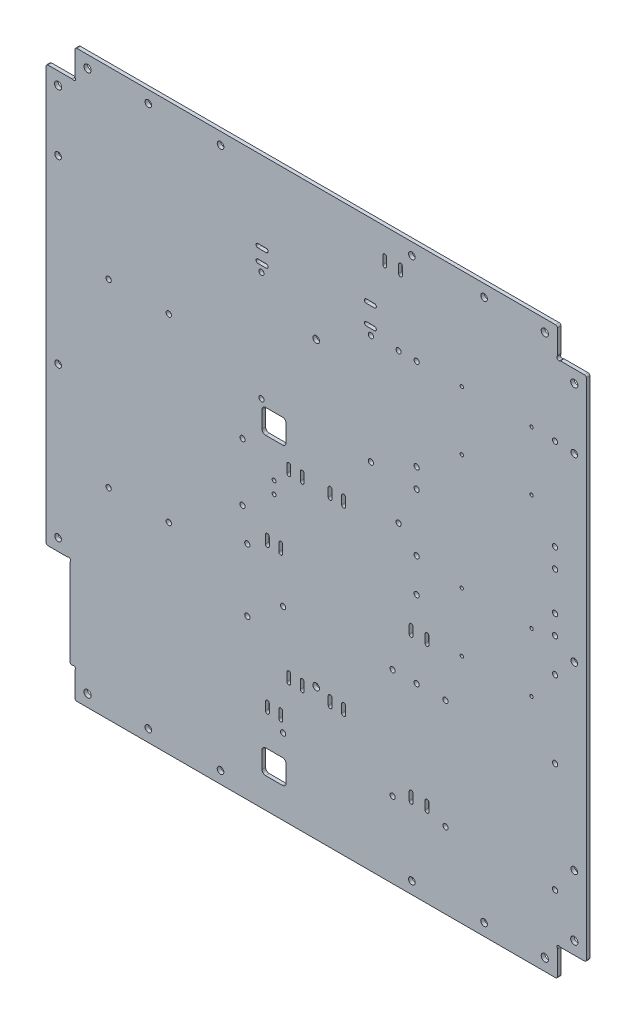
SolidWorks part; units mm, degrees
material "Acrylic (Medium-high impact)"
ref_plane "Front" through (0, 0, 0) normal (0, 0, 1) x (1, 0, 0)
ref_plane "Top" through (0, 0, 0) normal (0, 1, 0) x (1, 0, 0)
ref_plane "Right" through (0, 0, 0) normal (1, 0, 0) x (0, 0, -1)
sketch "Sketch2" plane through (0, 0, 0) normal (0, 0, 1) x (1, 0, 0)
  line L1 (0, 0) -> (449, 0)
  line L2 (0, 0) -> (0, 470)
  line L3 (0, 470) -> (449, 470)
  line L4 (449, 0) -> (449, 470)
  dimension "D1" = 449
  dimension "D2" = 470
extrude "Boss-Extrude1" add sketch "Sketch2" along normal blind 3
sketch "Sketch23" plane through (0, 0, 0) normal (0, 0, -1) x (-1, 0, 0)
  line L0 (-449, 470) -> (0, 470) construction
  line L1 (-449, 470) -> (-429, 470)
  line L2 (-449, 470) -> (-449, 450)
  line L3 (-449, 450) -> (-429, 450)
  line L4 (-429, 470) -> (-429, 450)
  line L5 (0, 470) -> (-20, 470)
  line L6 (0, 470) -> (0, 450)
  line L7 (0, 450) -> (-20, 450)
  line L8 (-20, 470) -> (-20, 450)
  line L9 (0, 470) -> (0, 0) construction
  line L11 (0, 0) -> (-20, 0)
  line L12 (0, 0) -> (0, 20)
  line L13 (0, 20) -> (-20, 20)
  line L14 (-20, 0) -> (-20, 20)
  line L15 (-449, 0) -> (-429, 0)
  line L16 (-449, 0) -> (-449, 20)
  line L17 (-449, 20) -> (-429, 20)
  line L18 (-429, 0) -> (-429, 20)
  dimension "D1" = 20
  dimension "D2" = 20
hole_wizard "M5 Clearance Hole1" positions "Sketch4" profile "Sketch5" hole size "M5" standard "ANSI Metric" end condition up to next
sketch "Sketch4" plane through (0, 0, 0) normal (0, 0, -1) x (-1, 0, 0)
  line L0 (-224.5, 470) -> (-224.5, 0) construction
  line L1 (-449, 470) -> (0, 470) construction
  line L2 (0, 0) -> (-449, 0) construction
  line L3 (-429, 460) -> (-364, 460) construction
  line L6 (-364, 460) -> (-85, 460) construction
  line L7 (-85, 460) -> (-20, 460) construction
  line L9 (-449, 235) -> (0, 235) construction
  line L10 (-449, 0) -> (-449, 470) construction
  line L12 (0, 470) -> (0, 0) construction
  line L13 (-439, 450) -> (-439, 20) construction
  line L18 (-10, 450) -> (-10, 20) construction
  line L21 (-429, 10) -> (-20, 10) construction
  line L31 (-20, 470) -> (-20, 450) construction
  line L32 (-429, 470) -> (-429, 450) construction
  line L33 (-449, 450) -> (-429, 450) construction
  line L34 (-449, 20) -> (-429, 20) construction
  line L35 (-429, 0) -> (-429, 20) construction
  line L36 (0, 450) -> (-20, 450) construction
  line L37 (0, 20) -> (-20, 20) construction
  line L38 (-20, 0) -> (-20, 20) construction
  point P13 (-224.5, 360)
  point P17 (-224.5, 110)
  point P24 (-364, 460)
  point P29 (-85, 460)
  point P54 (-304, 460)
  point P56 (-145, 460)
  point P59 (-85, 10)
  point P60 (-145, 10)
  point P61 (-304, 10)
  point P62 (-364, 10)
  point P83 (-439, 385)
  point P85 (-439, 85)
  point P92 (-10, 110)
  point P93 (-10, 385)
  point P97 (-439, 235)
  point P103 (-10, 235)
  dimension "D5" = 65
  dimension "D8" = 65
  dimension "D3" = 100
  dimension "D2" = 100
  dimension "D1" = 60
  dimension "D4" = 60
  dimension "D6" = 90
  dimension "D9" = 65
sketch "Sketch5" plane through (10, 235, 0) normal (1, 0, 0) x (0, 1, 0)
  line L0 (0, 0) -> (0, 3)
  line L1 (0, 3) -> (2.75, 3)
  line L2 (2.75, 3) -> (2.75, 0)
  line L5 (2.75, 0) -> (0, 0)
  line L11 (0, -6.35) -> (0, 107.95) construction
  dimension "Thru Hole Dia." = 5.5
  dimension "Thru Hole Depth" = 3
sketch "Sketch10" plane through (0, 0, 0) normal (0, 0, -1) x (-1, 0, 0)
  line L0 (-20, 20) -> (-429, 20) construction
  line L1 (-114.5, 26) -> (-69.5, 26) construction
  line L2 (-114.5, 26) -> (-114.5, 52) construction
  line L3 (-114.5, 52) -> (-69.5, 52) construction
  line L4 (-69.5, 26) -> (-69.5, 52) construction
  line L5 (-169.5, 45.65) -> (-175.85, 45.65)
  line L6 (-169.5, 52) -> (-214.5, 52) construction
  line L7 (-224.5, 20) -> (-224.5, 145.1565) construction
  line L8 (-108.15, 52) -> (-108.15, 45.65)
  line L13 (-169.5, 52) -> (-169.5, 26) construction
  line L15 (-119.5, 52) -> (-164.5, 52) construction
  line L16 (-119.5, 52) -> (-119.5, 26) construction
  line L17 (-119.5, 26) -> (-164.5, 26) construction
  line L18 (-164.5, 52) -> (-164.5, 26) construction
  line L22 (-108.15, 45.65) -> (-114.5, 45.65)
  line L23 (-114.5, 45.65) -> (-114.5, 32.35)
  line L24 (-114.5, 32.35) -> (-108.15, 32.35)
  line L25 (-108.15, 32.35) -> (-108.15, 26)
  line L26 (-108.15, 26) -> (-75.85, 26)
  line L27 (-75.85, 26) -> (-75.85, 32.35)
  line L28 (-75.85, 32.35) -> (-69.5, 32.35)
  line L29 (-69.5, 32.35) -> (-69.5, 45.65)
  line L30 (-69.5, 45.65) -> (-75.85, 45.65)
  line L31 (-75.85, 45.65) -> (-75.85, 52)
  line L32 (-75.85, 52) -> (-108.15, 52)
  line L33 (-158.15, 52) -> (-158.15, 45.65)
  line L34 (-158.15, 45.65) -> (-164.5, 45.65)
  line L35 (-164.5, 45.65) -> (-164.5, 32.35)
  line L36 (-164.5, 32.35) -> (-158.15, 32.35)
  line L37 (-158.15, 32.35) -> (-158.15, 26)
  line L38 (-158.15, 26) -> (-125.85, 26)
  line L39 (-125.85, 26) -> (-125.85, 32.35)
  line L40 (-125.85, 32.35) -> (-119.5, 32.35)
  line L41 (-119.5, 32.35) -> (-119.5, 45.65)
  line L42 (-119.5, 45.65) -> (-125.85, 45.65)
  line L43 (-125.85, 45.65) -> (-125.85, 52)
  line L44 (-125.85, 52) -> (-158.15, 52)
  line L45 (-284.5, 52) -> (-284.5, 26) construction
  line L46 (-329.5, 26) -> (-284.5, 26) construction
  line L47 (-329.5, 52) -> (-329.5, 26) construction
  line L48 (-329.5, 52) -> (-284.5, 52) construction
  line L49 (-379.5, 26) -> (-379.5, 52) construction
  line L50 (-334.5, 52) -> (-379.5, 52) construction
  line L51 (-334.5, 26) -> (-334.5, 52) construction
  line L52 (-334.5, 26) -> (-379.5, 26) construction
  line L53 (-323.15, 52) -> (-290.85, 52)
  line L54 (-323.15, 45.65) -> (-323.15, 52)
  line L55 (-329.5, 45.65) -> (-323.15, 45.65)
  line L56 (-329.5, 32.35) -> (-329.5, 45.65)
  line L57 (-323.15, 32.35) -> (-329.5, 32.35)
  line L58 (-323.15, 26) -> (-323.15, 32.35)
  line L59 (-290.85, 26) -> (-323.15, 26)
  line L60 (-290.85, 32.35) -> (-290.85, 26)
  line L61 (-284.5, 32.35) -> (-290.85, 32.35)
  line L62 (-284.5, 45.65) -> (-284.5, 32.35)
  line L63 (-290.85, 45.65) -> (-284.5, 45.65)
  line L64 (-290.85, 52) -> (-290.85, 45.65)
  line L65 (-373.15, 52) -> (-340.85, 52)
  line L66 (-373.15, 45.65) -> (-373.15, 52)
  line L67 (-379.5, 45.65) -> (-373.15, 45.65)
  line L68 (-379.5, 32.35) -> (-379.5, 45.65)
  line L69 (-373.15, 32.35) -> (-379.5, 32.35)
  line L70 (-373.15, 26) -> (-373.15, 32.35)
  line L71 (-340.85, 26) -> (-373.15, 26)
  line L72 (-340.85, 32.35) -> (-340.85, 26)
  line L73 (-334.5, 32.35) -> (-340.85, 32.35)
  line L74 (-334.5, 45.65) -> (-334.5, 32.35)
  line L75 (-340.85, 45.65) -> (-334.5, 45.65)
  line L76 (-340.85, 52) -> (-340.85, 45.65)
  line L77 (0, 0) -> (-449, 0) construction
  line L78 (-169.5, 26) -> (-214.5, 26) construction
  line L79 (-214.5, 52) -> (-214.5, 26) construction
  line L80 (-175.85, 45.65) -> (-175.85, 52)
  line L81 (-175.85, 52) -> (-208.15, 52)
  line L82 (-208.15, 52) -> (-208.15, 45.65)
  line L83 (-208.15, 45.65) -> (-214.5, 45.65)
  line L84 (-214.5, 45.65) -> (-214.5, 32.35)
  line L85 (-214.5, 32.35) -> (-208.15, 32.35)
  line L86 (-208.15, 32.35) -> (-208.15, 26)
  line L87 (-208.15, 26) -> (-175.85, 26)
  line L88 (-175.85, 26) -> (-175.85, 32.35)
  line L89 (-175.85, 32.35) -> (-169.5, 32.35)
  line L90 (-169.5, 32.35) -> (-169.5, 45.65)
  line L91 (-273.15, 32.35) -> (-279.5, 32.35)
  line L92 (-273.15, 26) -> (-273.15, 32.35)
  line L93 (-240.85, 26) -> (-273.15, 26)
  line L94 (-240.85, 32.35) -> (-240.85, 26)
  line L95 (-234.5, 32.35) -> (-240.85, 32.35)
  line L96 (-234.5, 45.65) -> (-234.5, 32.35)
  line L97 (-240.85, 45.65) -> (-234.5, 45.65)
  line L98 (-240.85, 52) -> (-240.85, 45.65)
  line L99 (-273.15, 52) -> (-240.85, 52)
  line L100 (-273.15, 45.65) -> (-273.15, 52)
  line L101 (-279.5, 45.65) -> (-273.15, 45.65)
  line L102 (-279.5, 32.35) -> (-279.5, 45.65)
  dimension "D2" = 45
  dimension "D4" = 26
  dimension "D1" = 6.35
  dimension "D5" = 5
  dimension "D6" = 26
  dimension "D3" = 5
  dimension "D7" = 20
extrude "extruder panel cutouts" [suppressed] cut sketch "Sketch10" against normal through all
sketch "Sketch16" [suppressed] plane through (0, 0, 0) normal (0, 0, -1) x (-1, 0, 0)
  line L0 (-373.15, 26) -> (-340.85, 26) construction
  line L1 (-366.5, 26) -> (-404.5, 26) construction
  line L2 (-366.5, 26) -> (-366.5, 52) construction
  line L3 (-366.5, 52) -> (-404.5, 52) construction
  line L4 (-404.5, 26) -> (-404.5, 52) construction
  line L6 (-398.15, 52) -> (-398.15, 45.65)
  line L7 (-398.15, 45.65) -> (-404.5, 45.65)
  line L8 (-404.5, 45.65) -> (-404.5, 32.35)
  line L9 (-404.5, 32.35) -> (-398.15, 32.35)
  line L10 (-398.15, 32.35) -> (-398.15, 26)
  line L11 (-398.15, 26) -> (-372.85, 26)
  line L12 (-372.85, 26) -> (-372.85, 32.35)
  line L13 (-372.85, 32.35) -> (-366.5, 32.35)
  line L14 (-366.5, 32.35) -> (-366.5, 45.65)
  line L15 (-366.5, 45.65) -> (-372.85, 45.65)
  line L16 (-372.85, 45.65) -> (-372.85, 52)
  line L17 (-372.85, 52) -> (-398.15, 52)
  line L18 (-449, 0) -> (-449, 470) construction
  dimension "D1" = 26
  dimension "D2" = 38
  dimension "D3" = 44.5
  dimension "D4" = 6.35
extrude "z_motor_panel_cutout" [suppressed] cut sketch "Sketch16" against normal blind 10
fillet "Fillet1" [suppressed] radius 3.175
fillet "Fillet3" [suppressed] radius 2
sketch "Sketch17" [suppressed] plane through (0, 0, 0) normal (0, 0, -1) x (-1, 0, 0)
  circle A4 centre (-376.325, 48.825) radius 1.55
  circle A5 centre (-337.675, 48.825) radius 1.55
  circle A6 centre (-337.675, 29.175) radius 1.55
  circle A7 centre (-376.325, 29.175) radius 1.55
  circle A8 centre (-326.325, 48.825) radius 1.55
  circle A9 centre (-287.675, 48.825) radius 1.55
  circle A10 centre (-287.675, 29.175) radius 1.55
  circle A11 centre (-326.325, 29.175) radius 1.55
  circle A12 centre (-161.325, 48.825) radius 1.55
  circle A13 centre (-122.675, 48.825) radius 1.55
  circle A14 centre (-122.675, 29.175) radius 1.55
  circle A15 centre (-161.325, 29.175) radius 1.55
  circle A16 centre (-111.325, 48.825) radius 1.55
  circle A17 centre (-72.675, 48.825) radius 1.55
  circle A18 centre (-72.675, 29.175) radius 1.55
  circle A19 centre (-111.325, 29.175) radius 1.55
  circle A20 centre (-276.325, 48.825) radius 1.55
  circle A21 centre (-276.325, 29.175) radius 1.55
  circle A22 centre (-237.675, 48.825) radius 1.55
  circle A23 centre (-237.675, 29.175) radius 1.55
  circle A24 centre (-211.325, 29.175) radius 1.55
  circle A25 centre (-211.325, 48.825) radius 1.55
  circle A26 centre (-172.675, 48.825) radius 1.55
  circle A27 centre (-172.675, 29.175) radius 1.55
  dimension "D1" = 3.1
extrude "Cut-Extrude3" [suppressed] cut sketch "Sketch17" against normal through all
sketch "Sketch7" plane through (0, 0, 0) normal (0, 0, -1) x (-1, 0, 0)
  line L0 (-449, 0) -> (-449, 470) construction
  line L1 (-423, 294) -> (-308, 294) construction
  line L2 (-423, 294) -> (-423, 386) construction
  line L3 (-423, 386) -> (-308, 386) construction
  line L4 (-308, 294) -> (-308, 386) construction
  line L5 (-423, 294) -> (-308, 386) construction
  line L6 (-423, 386) -> (-308, 294) construction
  line L7 (-304, 290) -> (-427, 290) construction
  line L8 (-304, 290) -> (-304, 390) construction
  line L9 (-304, 390) -> (-427, 390) construction
  line L10 (-427, 290) -> (-427, 390) construction
  line L11 (-304, 290) -> (-427, 390) construction
  line L12 (-304, 390) -> (-427, 290) construction
  line L14 (-423, 154) -> (-308, 154) construction
  line L15 (-423, 154) -> (-423, 246) construction
  line L16 (-423, 246) -> (-308, 246) construction
  line L17 (-308, 154) -> (-308, 246) construction
  line L18 (-423, 154) -> (-308, 246) construction
  line L19 (-423, 246) -> (-308, 154) construction
  line L20 (-304, 150) -> (-427, 150) construction
  line L21 (-304, 150) -> (-304, 250) construction
  line L22 (-304, 250) -> (-427, 250) construction
  line L23 (-427, 150) -> (-427, 250) construction
  line L24 (-304, 150) -> (-427, 250) construction
  line L25 (-304, 250) -> (-427, 150) construction
  circle A0 centre (-423, 386) radius 2.15
  circle A1 centre (-308, 386) radius 2.15
  circle A2 centre (-308, 294) radius 2.15
  circle A3 centre (-423, 294) radius 2.15
  circle A4 centre (-423, 246) radius 2.15
  circle A5 centre (-308, 246) radius 2.15
  circle A6 centre (-308, 154) radius 2.15
  circle A7 centre (-423, 154) radius 2.15
  point P0 (-365.5, 340)
  point P6 (-365.5, 340)
  point P19 (-365.5, 200)
  point P25 (-365.5, 200)
  dimension "D5" = 4.3
  dimension "D12" = 4.3
  dimension "D1" = 115
  dimension "D2" = 92
  dimension "D3" = 123
  dimension "D4" = 100
  dimension "D6" = 22
  dimension "D7" = 60
  dimension "D8" = 115
  dimension "D9" = 92
  dimension "D10" = 123
  dimension "D13" = 40
extrude "Duet2 mounting holes" cut sketch "Sketch7" against normal through all
sketch "Sketch9" plane through (0, 0, 0) normal (0, 0, -1) x (-1, 0, 0)
  line L0 (0, 470) -> (0, 0) construction
  line L1 (-102, 167) -> (-52, 167) construction
  line L2 (-102, 167) -> (-102, 317) construction
  line L3 (-102, 317) -> (-52, 317) construction
  line L4 (-52, 167) -> (-52, 317) construction
  line L5 (-102, 167) -> (-52, 317) construction
  line L6 (-102, 317) -> (-52, 167) construction
  line L8 (0, 0) -> (-449, 0) construction
  line L9 (-20, 135) -> (-134, 135) construction
  line L10 (-20, 135) -> (-20, 349) construction
  line L11 (-20, 349) -> (-134, 349) construction
  line L12 (-134, 135) -> (-134, 349) construction
  line L13 (-20, 135) -> (-134, 349) construction
  line L14 (-20, 349) -> (-134, 135) construction
  circle A0 centre (-52, 317) radius 2.2
  circle A1 centre (-102, 317) radius 2.2
  circle A2 centre (-52, 167) radius 2.2
  circle A3 centre (-102, 167) radius 2.2
  point P0 (-77, 242)
  point P11 (-77, 242)
  point P21 (-77, 317)
  dimension "D1" = 50
  dimension "D3" = 4.4
  dimension "D2" = 114
  dimension "D4" = 32
  dimension "D5" = 150
  dimension "D6" = 20
  dimension "D7" = 135
extrude "psu mounting holes" cut sketch "Sketch9" against normal through all
sketch "Sketch11" plane through (0, 0, 0) normal (0, 0, -1) x (-1, 0, 0)
  line L0 (-224.5, 0) -> (-224.5, 150.8562) construction
  line L1 (0, 0) -> (-449, 0) construction
  line L2 (-163.25, 210) -> (-163.25, 258) construction
  circle A0 centre (-163.25, 258) radius 2.15
  circle A1 centre (-163.25, 210) radius 2.15
  dimension "D1" = 48
  dimension "D2" = 4.3
  dimension "D3" = 210
  dimension "D4" = 61.25
extrude "ssr holes" cut sketch "Sketch11" against normal through all
sketch "Sketch27" plane through (0, 0, 0) normal (0, 0, -1) x (-1, 0, 0)
  line L0 (-167.25, 184.15) -> (-167.25, 132.15) construction
  line L1 (-20, 135) -> (-134, 135) construction
  line L2 (-180.5, 135) -> (-154, 135) construction
  line L3 (-180.5, 135) -> (-180.5, 181.3) construction
  line L4 (-180.5, 181.3) -> (-154, 181.3) construction
  line L5 (-154, 135) -> (-154, 181.3) construction
  line L6 (-180.5, 135) -> (-154, 181.3) construction
  line L7 (-180.5, 181.3) -> (-154, 135) construction
  line L8 (-134, 135) -> (-134, 349) construction
  circle A0 centre (-167.25, 184.15) radius 2.15
  circle A1 centre (-167.25, 132.15) radius 2.15
  point P4 (-167.25, 158.15)
  dimension "D1" = 52
  dimension "D2" = 4.3
  dimension "D3" = 46.3
  dimension "D4" = 26.5
  dimension "D5" = 20
extrude "5V DC/DC Converter for Raspi" cut sketch "Sketch27" against normal through all
sketch "Sketch18" plane through (0, 0, 0) normal (0, 0, -1) x (-1, 0, 0)
  line L0 (-423, 262) -> (-293, 262) construction
  line L1 (-423, 386) -> (-293, 386) construction
  line L2 (-428, 391) -> (-288, 391) construction
  line L3 (-423, 386) -> (-293, 386) construction
  line L4 (-423, 386) -> (-423, 262) construction
  line L5 (-423, 262) -> (-293, 262) construction
  line L6 (-293, 386) -> (-293, 262) construction
  line L7 (-288, 391) -> (-288, 257) construction
  line L8 (-428, 257) -> (-288, 257) construction
  line L9 (-428, 391) -> (-428, 257) construction
  line L18 (-423, 63) -> (-423, 154) construction
  line L19 (-427.5, 58.5) -> (-327.5, 58.5) construction
  line L20 (-427.5, 58.5) -> (-427.5, 158.5) construction
  line L21 (-427.5, 158.5) -> (-327.5, 158.5) construction
  line L22 (-327.5, 58.5) -> (-327.5, 158.5) construction
  line L23 (-423, 154) -> (-332, 154) construction
  line L24 (-332, 63) -> (-332, 154) construction
  line L25 (-423, 63) -> (-332, 63) construction
  line L26 (-192.5, 158.5) -> (-292.5, 158.5) construction
  line L27 (-197, 154) -> (-288, 154) construction
  line L28 (-197, 154) -> (-197, 63) construction
  line L29 (-197, 63) -> (-288, 63) construction
  line L30 (-288, 154) -> (-288, 63) construction
  line L31 (-292.5, 158.5) -> (-292.5, 58.5) construction
  line L32 (-192.5, 58.5) -> (-292.5, 58.5) construction
  line L33 (-192.5, 158.5) -> (-192.5, 58.5) construction
  circle A0 centre (-293, 386) radius 2.15
  circle A1 centre (-423, 386) radius 2.15 construction
  circle A2 centre (-293, 262) radius 2.15
  circle A7 centre (-332, 154) radius 2.15
  circle A8 centre (-332, 63) radius 2.15
  circle A9 centre (-423, 63) radius 2.15
  circle A10 centre (-423, 154) radius 2.15 construction
  circle A11 centre (-288, 154) radius 2.15
  circle A12 centre (-288, 63) radius 2.15
  circle A13 centre (-197, 63) radius 2.15
  circle A14 centre (-163.25, 258) radius 2.15 construction
  circle A15 centre (-197, 154) radius 2.15
  circle A20 centre (-423, 262) radius 2.15
  dimension "D2" = 4.3
  dimension "D1" = 130
  dimension "D3" = 124
  dimension "D14" = 100
  dimension "D16" = 91
  dimension "D17" = 91
  dimension "D19" = 35
  dimension "D4" = 5
  dimension "D15" = 4.5
  dimension "D18" = 4.5
extrude "Duet3, Mini, and Expanders" cut sketch "Sketch18" against normal through all
sketch "Sketch25" plane through (0, 0, 0) normal (0, 0, -1) x (-1, 0, 0)
  line L0 (-403.5, 386.5) -> (-345.5, 386.5) construction
  line L1 (-427, 390) -> (-342, 390) construction
  line L2 (-427, 390) -> (-427, 334) construction
  line L3 (-427, 334) -> (-342, 334) construction
  line L4 (-342, 390) -> (-342, 334) construction
  line L5 (-345.5, 386.5) -> (-345.5, 337.5) construction
  line L6 (-345.5, 337.5) -> (-403.5, 337.5) construction
  line L7 (-403.5, 337.5) -> (-403.5, 386.5) construction
  line L8 (-403.5, 241.5) -> (-345.5, 241.5) construction
  line L9 (-427, 245) -> (-342, 245) construction
  line L10 (-427, 245) -> (-427, 189) construction
  line L11 (-427, 189) -> (-342, 189) construction
  line L12 (-342, 245) -> (-342, 189) construction
  line L13 (-345.5, 241.5) -> (-345.5, 192.5) construction
  line L14 (-345.5, 192.5) -> (-403.5, 192.5) construction
  line L15 (-403.5, 192.5) -> (-403.5, 241.5) construction
  line L16 (-427, 150) -> (-427, 250) construction
  line L17 (-428, 257) -> (-288, 257) construction
  circle A0 centre (-403.5, 386.5) radius 1.35
  circle A1 centre (-345.5, 386.5) radius 1.35
  circle A2 centre (-345.5, 337.5) radius 1.35
  circle A3 centre (-403.5, 337.5) radius 1.35
  circle A4 centre (-403.5, 241.5) radius 1.35
  circle A5 centre (-345.5, 241.5) radius 1.35
  circle A6 centre (-345.5, 192.5) radius 1.35
  circle A7 centre (-403.5, 192.5) radius 1.35
  dimension "D6" = 2.7
  dimension "D1" = 85
  dimension "D2" = 56
  dimension "D3" = 3.5
  dimension "D4" = 3.5
  dimension "D5" = 58
  dimension "D7" = 3.5
  dimension "D8" = 85
  dimension "D9" = 56
  dimension "D10" = 3.5
  dimension "D11" = 3.5
  dimension "D12" = 58
  dimension "D14" = 3.5
  dimension "D15" = 12
extrude "Raspi Options" cut sketch "Sketch25" against normal through all
sketch "Sketch26" plane through (0, 0, 0) normal (0, 0, -1) x (-1, 0, 0)
  line L0 (-270, 385.5) -> (-179, 385.5) construction
  line L1 (-274.5, 290) -> (-174.5, 290) construction
  line L2 (-274.5, 290) -> (-274.5, 390) construction
  line L3 (-274.5, 390) -> (-174.5, 390) construction
  line L4 (-174.5, 290) -> (-174.5, 390) construction
  line L5 (-179, 294.5) -> (-179, 385.5) construction
  line L6 (-270, 294.5) -> (-179, 294.5) construction
  line L7 (-270, 294.5) -> (-270, 385.5) construction
  line L8 (-192.5, 158.5) -> (-292.5, 158.5) construction
  line L9 (-192.5, 158.5) -> (-192.5, 58.5) construction
  line L10 (-197, 154) -> (-288, 154) construction
  line L11 (-197, 154) -> (-197, 63) construction
  line L12 (-224.5, 470) -> (-224.5, 0) construction
  line L13 (-304, 390) -> (-427, 390) construction
  line L14 (-423, 218) -> (-308, 218) construction
  line L15 (-423, 218) -> (-423, 310) construction
  line L16 (-423, 310) -> (-308, 310) construction
  line L17 (-308, 218) -> (-308, 310) construction
  line L18 (-423, 218) -> (-308, 310) construction
  line L19 (-423, 310) -> (-308, 218) construction
  line L20 (-304, 214) -> (-427, 214) construction
  line L21 (-304, 214) -> (-304, 314) construction
  line L22 (-304, 314) -> (-427, 314) construction
  line L23 (-427, 214) -> (-427, 314) construction
  line L24 (-304, 214) -> (-427, 314) construction
  line L25 (-304, 314) -> (-427, 214) construction
  line L26 (-427, 290) -> (-427, 390) construction
  line L27 (-427, 334) -> (-342, 334) construction
  circle A0 centre (-179, 385.5) radius 2.15
  circle A1 centre (-270, 385.5) radius 2.15
  circle A2 centre (-179, 294.5) radius 2.15
  circle A3 centre (-270, 294.5) radius 2.15
  circle A4 centre (-197, 154) radius 2.15 construction
  circle A5 centre (-423, 310) radius 2.15
  circle A6 centre (-308, 310) radius 2.15
  circle A7 centre (-308, 218) radius 2.15
  circle A8 centre (-423, 218) radius 2.15
  point P0 (-224.5, 390)
  point P27 (-365.5, 264)
  point P33 (-365.5, 264)
  dimension "D7" = 4.3
  dimension "D1" = 4.5
  dimension "D2" = 4.5
  dimension "D3" = 115
  dimension "D4" = 92
  dimension "D5" = 123
  dimension "D6" = 100
  dimension "D8" = 20
extrude "Duet3 Mini and 3HC" cut sketch "Sketch26" against normal through all
sketch "Sketch12" plane through (0, 0, 0) normal (0, 0, -1) x (-1, 0, 0)
  line L0 (-414.5, 460) -> (-429, 460) construction
  line L2 (-20, 460) -> (-34.5, 460) construction
  line L4 (-439, 450) -> (-439, 435.5) construction
  line L6 (-439, 20) -> (-439, 34.5) construction
  line L8 (-429, 10) -> (-414.5, 10) construction
  line L10 (-20, 10) -> (-34.5, 10) construction
  line L12 (-10, 20) -> (-10, 34.5) construction
  line L14 (-10, 450) -> (-10, 435.5) construction
  line L19 (-429, 0) -> (-429, 20) construction
  circle A0 centre (-414.5, 460) radius 3
  circle A1 centre (-34.5, 460) radius 3
  circle A2 centre (-439, 435.5) radius 3
  circle A3 centre (-439, 34.5) radius 3
  circle A4 centre (-414.5, 10) radius 3
  circle A5 centre (-34.5, 10) radius 3
  circle A6 centre (-10, 34.5) radius 3
  circle A7 centre (-10, 435.5) radius 3
  dimension "D1" = 14.5
  dimension "D2" = 6
extrude "inside corner bracket screw clearance holes" cut sketch "Sketch12" against normal through all
sketch "Sketch6" plane through (0, 0, 0) normal (0, 0, -1) x (-1, 0, 0)
  line L0 (-224.5, 470) -> (-224.5, 0) construction
  line L1 (-449, 470) -> (0, 470) construction
  line L2 (-449, 470) -> (0, 470) construction
  line L3 (-274.5, 290) -> (-274.5, 390) construction
  line L4 (-429, 450) -> (-20, 450) construction
  line L5 (-245.675, 260) -> (-245.675, 250)
  line L14 (-245.675, 260) -> (-248.85, 260)
  line L15 (-248.85, 260) -> (-248.85, 250)
  line L16 (-245.675, 250) -> (-248.85, 250)
  line L17 (-234.5, 260) -> (-234.5, 250)
  line L18 (-234.5, 260) -> (-237.675, 260)
  line L19 (-237.675, 260) -> (-237.675, 250)
  line L20 (-234.5, 250) -> (-237.675, 250)
  line L85 (-245.675, 110) -> (-245.675, 100)
  line L86 (-245.675, 100) -> (-248.85, 100)
  line L87 (-248.85, 110) -> (-248.85, 100)
  line L88 (-245.675, 110) -> (-248.85, 110)
  line L89 (-234.5, 110) -> (-234.5, 100)
  line L90 (-234.5, 100) -> (-237.675, 100)
  line L91 (-237.675, 110) -> (-237.675, 100)
  line L92 (-234.5, 110) -> (-237.675, 110)
  line L105 (-174.5, 401.65) -> (-174.5, 404.825)
  line L106 (-274.5, 390.475) -> (-264.5, 390.475)
  line L107 (-274.5, 390.475) -> (-274.5, 393.65)
  line L108 (-274.5, 393.65) -> (-264.5, 393.65)
  line L109 (-264.5, 390.475) -> (-264.5, 393.65)
  line L110 (-264.5, 406.825) -> (-274.5, 406.825)
  line L111 (-264.5, 406.825) -> (-264.5, 410)
  line L112 (-264.5, 410) -> (-274.5, 410)
  line L113 (-274.5, 406.825) -> (-274.5, 410)
  line L114 (-184.5, 404.825) -> (-174.5, 404.825)
  line L115 (-184.5, 401.65) -> (-184.5, 404.825)
  line L116 (-184.5, 401.65) -> (-174.5, 401.65)
  line L117 (-184.5, 390.475) -> (-184.5, 393.65)
  line L118 (-174.5, 393.65) -> (-184.5, 393.65)
  line L119 (-174.5, 390.475) -> (-174.5, 393.65)
  line L120 (-174.5, 390.475) -> (-184.5, 390.475)
  line L121 (-174.5, 290) -> (-174.5, 390) construction
  line L122 (-224.5, 470) -> (-224.5, 0) construction
  line L123 (-214.5, 110) -> (-211.325, 110)
  line L124 (-211.325, 110) -> (-211.325, 100)
  line L125 (-214.5, 100) -> (-211.325, 100)
  line L126 (-214.5, 110) -> (-214.5, 100)
  line L127 (-203.325, 110) -> (-200.15, 110)
  line L128 (-200.15, 110) -> (-200.15, 100)
  line L133 (-316.5875, 70) -> (-327.5, 70) construction
  line L134 (-292.5, 158.5) -> (-292.5, 58.5) construction
  line L135 (-327.5, 58.5) -> (-327.5, 158.5) construction
  line L136 (0, 0) -> (-449, 0) construction
  line L137 (-318.175, 65) -> (-315, 65)
  line L138 (-318.175, 65) -> (-318.175, 75)
  line L139 (-318.175, 75) -> (-315, 75)
  line L140 (-315, 65) -> (-315, 75)
  line L141 (-318.175, 65) -> (-315, 75) construction
  line L142 (-318.175, 75) -> (-315, 65) construction
  line L143 (-305, 65) -> (-301.825, 65)
  line L144 (-305, 65) -> (-305, 75)
  line L145 (-305, 75) -> (-301.825, 75)
  line L146 (-301.825, 65) -> (-301.825, 75)
  line L147 (-305, 65) -> (-301.825, 75) construction
  line L148 (-305, 75) -> (-301.825, 65) construction
  line L149 (-316.5875, 70) -> (-303.4125, 70) construction
  line L150 (-303.4125, 70) -> (-292.5, 70) construction
  line L151 (-288, 445) -> (-288, 391) construction
  line L152 (-316.5875, 190) -> (-327.5, 190) construction
  line L153 (-318.175, 185) -> (-315, 185)
  line L154 (-318.175, 185) -> (-318.175, 195)
  line L155 (-318.175, 195) -> (-315, 195)
  line L156 (-315, 185) -> (-315, 195)
  line L157 (-318.175, 185) -> (-315, 195) construction
  line L158 (-318.175, 195) -> (-315, 185) construction
  line L159 (-305, 185) -> (-301.825, 185)
  line L160 (-305, 185) -> (-305, 195)
  line L161 (-305, 195) -> (-301.825, 195)
  line L162 (-301.825, 185) -> (-301.825, 195)
  line L163 (-305, 185) -> (-301.825, 195) construction
  line L164 (-305, 195) -> (-301.825, 185) construction
  line L165 (-316.5875, 190) -> (-303.4125, 190) construction
  line L166 (-303.4125, 190) -> (-292.5, 190) construction
  line L167 (-296.175, 440) -> (-293, 440)
  line L168 (-296.175, 440) -> (-296.175, 450)
  line L169 (-296.175, 450) -> (-293, 450)
  line L170 (-293, 440) -> (-293, 450)
  line L171 (-296.175, 440) -> (-293, 450) construction
  line L172 (-296.175, 450) -> (-293, 440) construction
  line L173 (-283, 440) -> (-279.825, 440)
  line L174 (-283, 440) -> (-283, 450)
  line L175 (-283, 450) -> (-279.825, 450)
  line L176 (-279.825, 440) -> (-279.825, 450)
  line L177 (-283, 440) -> (-279.825, 450) construction
  line L178 (-283, 450) -> (-279.825, 440) construction
  line L179 (-294.5875, 445) -> (-281.4125, 445) construction
  line L180 (-203.325, 100) -> (-200.15, 100)
  line L181 (-203.325, 110) -> (-203.325, 100)
  line L182 (-214.5, 250) -> (-211.325, 250)
  line L183 (-211.325, 260) -> (-211.325, 250)
  line L184 (-214.5, 260) -> (-211.325, 260)
  line L185 (-214.5, 260) -> (-214.5, 250)
  line L186 (-203.325, 250) -> (-200.15, 250)
  line L187 (-200.15, 260) -> (-200.15, 250)
  line L188 (-203.325, 260) -> (-200.15, 260)
  line L189 (-203.325, 260) -> (-203.325, 250)
  point P82 (-316.5875, 70)
  point P87 (-303.4125, 70)
  point P118 (-316.5875, 190)
  point P123 (-303.4125, 190)
  point P138 (-294.5875, 445)
  point P143 (-281.4125, 445)
  dimension "D11" = 13.175
  dimension "D12" = 60
  dimension "D14" = 70
  dimension "D15" = 120
  dimension "D2" = 8
  dimension "D3" = 10
  dimension "D4" = 210
  dimension "D5" = 3.175
  dimension "D6" = 10
  dimension "D7" = 8
  dimension "D9" = 13.175
  dimension "D10" = 100
extrude "main wiring tie-downs" cut sketch "Sketch6" against normal through all
sketch "Sketch13" plane through (0, 0, 0) normal (0, 0, -1) x (-1, 0, 0)
  line L1 (-449, 0) -> (-425, 0)
  line L2 (-449, 0) -> (-449, 24)
  line L3 (-449, 24) -> (-425, 24)
  line L4 (-425, 0) -> (-425, 24)
  line L5 (0, 0) -> (-24, 0)
  line L6 (0, 0) -> (0, 24)
  line L7 (0, 24) -> (-24, 24)
  line L8 (-24, 0) -> (-24, 24)
  line L12 (-429, 0) -> (-429, 20) construction
  line L15 (-449, 470) -> (-425, 470)
  line L16 (-449, 470) -> (-449, 446)
  line L17 (-449, 446) -> (-425, 446)
  line L18 (-425, 470) -> (-425, 446)
  line L19 (0, 470) -> (-24, 470)
  line L20 (0, 470) -> (0, 446)
  line L21 (0, 446) -> (-24, 446)
  line L22 (-24, 470) -> (-24, 446)
  line L24 (-449, 20) -> (-429, 20) construction
  line L25 (0, 20) -> (-20, 20) construction
  line L26 (-449, 450) -> (-429, 450) construction
  line L27 (0, 450) -> (-20, 450) construction
  dimension "3" = 4
  dimension "D1" = 4
  dimension "D2" = 4
  dimension "D3" = 4
  dimension "D4" = 4
extrude "Cut-Extrude1" cut sketch "Sketch13" against normal through all
fillet "Fillet4" radius 1.5875 72 edges at (234.5, 250, 1.5) (245.675, 250, 1.5) (248.85, 250, 1.5) (237.675, 250, 1.5) (237.675, 260, 1.5) (248.85, 260, 1.5) (245.675, 260, 1.5) (234.5, 260, 1.5) (264.5, 393.65, 1.5) (264.5, 410, 1.5) (274.5, 406.825, 1.5) (274.5, 390.475, 1.5) (274.5, 393.65, 1.5) (274.5, 410, 1.5) (264.5, 390.475, 1.5) (264.5, 406.825, 1.5) (174.5, 390.475, 1.5) (174.5, 393.65, 1.5) (184.5, 393.65, 1.5) (184.5, 390.475, 1.5) (184.5, 401.65, 1.5) (174.5, 401.65, 1.5) (174.5, 404.825, 1.5) (184.5, 404.825, 1.5) (245.675, 100, 1.5) (248.85, 100, 1.5) (248.85, 110, 1.5) (245.675, 110, 1.5) (237.675, 100, 1.5) (234.5, 100, 1.5) (237.675, 110, 1.5) (234.5, 110, 1.5) (318.175, 75, 1.5) (315, 75, 1.5) (305, 75, 1.5) (301.825, 75, 1.5) (318.175, 65, 1.5) (315, 65, 1.5) (305, 65, 1.5) (301.825, 65, 1.5) (301.825, 185, 1.5) (315, 185, 1.5) (318.175, 185, 1.5) (305, 185, 1.5) (315, 195, 1.5) (318.175, 195, 1.5) (305, 195, 1.5) (301.825, 195, 1.5) (296.175, 440, 1.5) (283, 440, 1.5) (279.825, 440, 1.5) (293, 440, 1.5) (293, 450, 1.5) (296.175, 450, 1.5) (283, 450, 1.5) (279.825, 450, 1.5) (203.325, 100, 1.5) (214.5, 100, 1.5) (211.325, 110, 1.5) (200.15, 110, 1.5) (214.5, 110, 1.5) (203.325, 110, 1.5) (211.325, 100, 1.5) (200.15, 100, 1.5) (200.15, 250, 1.5) (211.325, 250, 1.5) (203.325, 250, 1.5) (214.5, 250, 1.5) (211.325, 260, 1.5) (214.5, 260, 1.5) (203.325, 260, 1.5) (200.15, 260, 1.5)
sketch "Sketch19" plane through (0, 0, 0) normal (0, 0, -1) x (-1, 0, 0)
  line L0 (0, 0) -> (-20, 0) construction
  line L1 (-20, 100) -> (0, 100)
  line L2 (-20, 100) -> (-20, 0)
  line L3 (-20, 0) -> (0, 0)
  line L4 (0, 100) -> (0, 0)
  line L6 (0, 446) -> (0, 24) construction
  dimension "D3" = 100
extrude "power inlet socket cutout" cut sketch "Sketch19" against normal through all
sketch "Sketch20" plane through (0, 0, 0) normal (0, 0, -1) x (-1, 0, 0)
  line L0 (-189.5, 266.4269) -> (-189.5, 0) construction
  line L1 (-179.5, 290) -> (-199.5, 290)
  line L2 (-179.5, 290) -> (-179.5, 270)
  line L3 (-179.5, 270) -> (-199.5, 270)
  line L4 (-199.5, 290) -> (-199.5, 270)
  line L5 (-189.5, 270) -> (-189.5, 290) construction
  line L6 (-224.5, 470) -> (-224.5, 0) construction
  line L7 (-449, 235) -> (0, 235) construction
  line L8 (-24, 0) -> (-425, 0) construction
  line L9 (-185.5, 190) -> (-182.325, 190)
  line L10 (-193.5, 200) -> (-196.675, 200)
  line L11 (-193.5, 200) -> (-193.5, 190)
  line L12 (-193.5, 190) -> (-196.675, 190)
  line L13 (-196.675, 200) -> (-196.675, 190)
  line L18 (-182.325, 200) -> (-182.325, 190)
  line L19 (-185.5, 200) -> (-182.325, 200)
  line L20 (-185.5, 200) -> (-185.5, 190)
  line L21 (-185.5, 70) -> (-182.325, 70)
  line L22 (-193.5, 80) -> (-196.675, 80)
  line L23 (-193.5, 80) -> (-193.5, 70)
  line L24 (-193.5, 70) -> (-196.675, 70)
  line L25 (-196.675, 80) -> (-196.675, 70)
  line L26 (-182.325, 80) -> (-182.325, 70)
  line L27 (-185.5, 80) -> (-182.325, 80)
  line L28 (-185.5, 80) -> (-185.5, 70)
  line L30 (-199.5, 25) -> (-179.5, 25)
  line L31 (-199.5, 25) -> (-199.5, 45)
  line L32 (-199.5, 45) -> (-179.5, 45)
  line L33 (-179.5, 25) -> (-179.5, 45)
  line L34 (-199.5, 25) -> (-179.5, 45) construction
  line L35 (-199.5, 45) -> (-179.5, 25) construction
  point P22 (-189.5, 35)
  dimension "D1" = 35
  dimension "D2" = 20
  dimension "D3" = 35
  dimension "D4" = 20
  dimension "D6" = 8
  dimension "D8" = 3.175
  dimension "D5" = 70
  dimension "D9" = 10
  dimension "D10" = 25
extrude "Bed Heater Holes" cut sketch "Sketch20" against normal through all
fillet "Fillet6" radius 3 8 edges at (179.5, 270, 1.5) (179.5, 290, 1.5) (199.5, 290, 1.5) (199.5, 270, 1.5) (179.5, 25, 1.5) (199.5, 25, 1.5) (199.5, 45, 1.5) (179.5, 45, 1.5)
sketch "Sketch22" plane through (0, 0, 0) normal (0, 0, -1) x (-1, 0, 0)
  line L0 (-189.5, 241) -> (-189.5, 231) construction
  line L1 (-196.5, 270) -> (-182.5, 270) construction
  line L2 (-189.5, 241) -> (-189.5, 270) construction
  circle A0 centre (-189.5, 241) radius 1.6
  circle A1 centre (-189.5, 231) radius 1.6
  dimension "D1" = 3.2
  dimension "D3" = 29
  dimension "D2" = 10
extrude "Cable Chain Attachment Points" cut sketch "Sketch22" against normal through all
fillet "Fillet7" radius 1.5875 25 edges at (449, 24, 1.5) (425, 0, 1.5) (24, 0, 1.5) (20, 24, 1.5) (0, 100, 1.5) (0, 446, 1.5) (24, 470, 1.5) (449, 446, 1.5) (425, 470, 1.5) (193.5, 190, 1.5) (182.325, 190, 1.5) (196.675, 200, 1.5) (185.5, 200, 1.5) (182.325, 200, 1.5) (193.5, 200, 1.5) (185.5, 190, 1.5) (196.675, 190, 1.5) (185.5, 70, 1.5) (196.675, 70, 1.5) (182.325, 70, 1.5) (193.5, 70, 1.5) (182.325, 80, 1.5) (193.5, 80, 1.5) (185.5, 80, 1.5) (196.675, 80, 1.5)
other "Move Face1" [suppressed] offset 0.0762 parameters "D1"=0.0762
sketch "Sketch24" plane through (0, 0, 0) normal (0, 0, -1) x (-1, 0, 0)
  line L0 (-24, 446) -> (-22.8757, 447.1243) construction
  line L1 (-1.5875, 100) -> (-20, 100) construction
  line L2 (-18.8775, 98.8775) -> (-20, 100) construction
  line L3 (-24, 24) -> (-22.8757, 22.8757) construction
  line L5 (-21.5875, 24) -> (-24, 24) construction
  line L8 (-24, 446) -> (-1.5875, 446) construction
  line L11 (-425, 446) -> (-426.1243, 447.1243) construction
  line L12 (-447.4125, 446) -> (-425, 446) construction
  line L15 (-425, 24) -> (-426.1243, 22.8757) construction
  line L16 (-425, 24) -> (-447.4125, 24) construction
  circle A10 centre (-18.8775, 98.8775) radius 1.5875
  circle A11 centre (-22.8757, 447.1243) radius 1.59
  circle A12 centre (-426.1243, 447.1243) radius 1.59
  circle A13 centre (-426.1243, 22.8757) radius 1.59
  circle A14 centre (-22.8757, 22.8757) radius 1.59
  dimension "D2" = 45
  dimension "D6" = 1.5875
  dimension "D7" = 45
  dimension "D8" = 1.59
  dimension "D9" = 45
  dimension "D10" = 1.59
  dimension "D11" = 45
  dimension "D12" = 1.59
  dimension "D3" = 45
  dimension "D4" = 1.59
extrude "Cut-Extrude6" cut sketch "Sketch24" against normal through all
fillet "Fillet8" radius 1 10 edges at (20, 97.7549, 1.5) (17.7549, 100, 1.5) (427.2486, 446, 1.5) (425, 448.2486, 1.5) (21.7514, 446, 1.5) (24, 448.2486, 1.5) (427.2486, 24, 1.5) (425, 21.7514, 1.5) (24, 21.7514, 1.5) (21.7514, 24, 1.5)
equation "\"D8@Sketch4\"=\"D5@Sketch4\""
equation "\"D2@Sketch4\"=\"D3@Sketch4\""
equation "\"D4@Sketch4\"=\"D1@Sketch4\""
equation "\"D18@Sketch18\"=\"D15@Sketch18\""
equation "\"D9@Sketch4\"=\"D8@Sketch4\""
equation "\"D1@Sketch13\"=\"3@Sketch13\""
equation "\"D2@Sketch13\"=\"3@Sketch13\""
equation "\"D3@Sketch13\"=\"3@Sketch13\""
equation "\"D4@Sketch13\"=\"3@Sketch13\""
equation "\"cutter_diameter\"=3.175"
equation "\"D1@Fillet4\"=\"cutter_diameter\"/2"
equation "\"D6@Sketch24\"=\"cutter_diameter\"/2"
equation "\"D7@Sketch6\"=\"D2@Sketch6\""
equation "\"D9@Sketch6\"=10 + \"cutter_diameter\""
equation "\"D8@Sketch20\"=\"cutter_diameter\""
equation "\"D1@Fillet7\"=\"cutter_diameter\"/2"
equation "\"DC2@Fillet7\"=\"cutter_diameter\"/2"
equation "\"D3@Sketch10\"=\"D5@Sketch10\""
